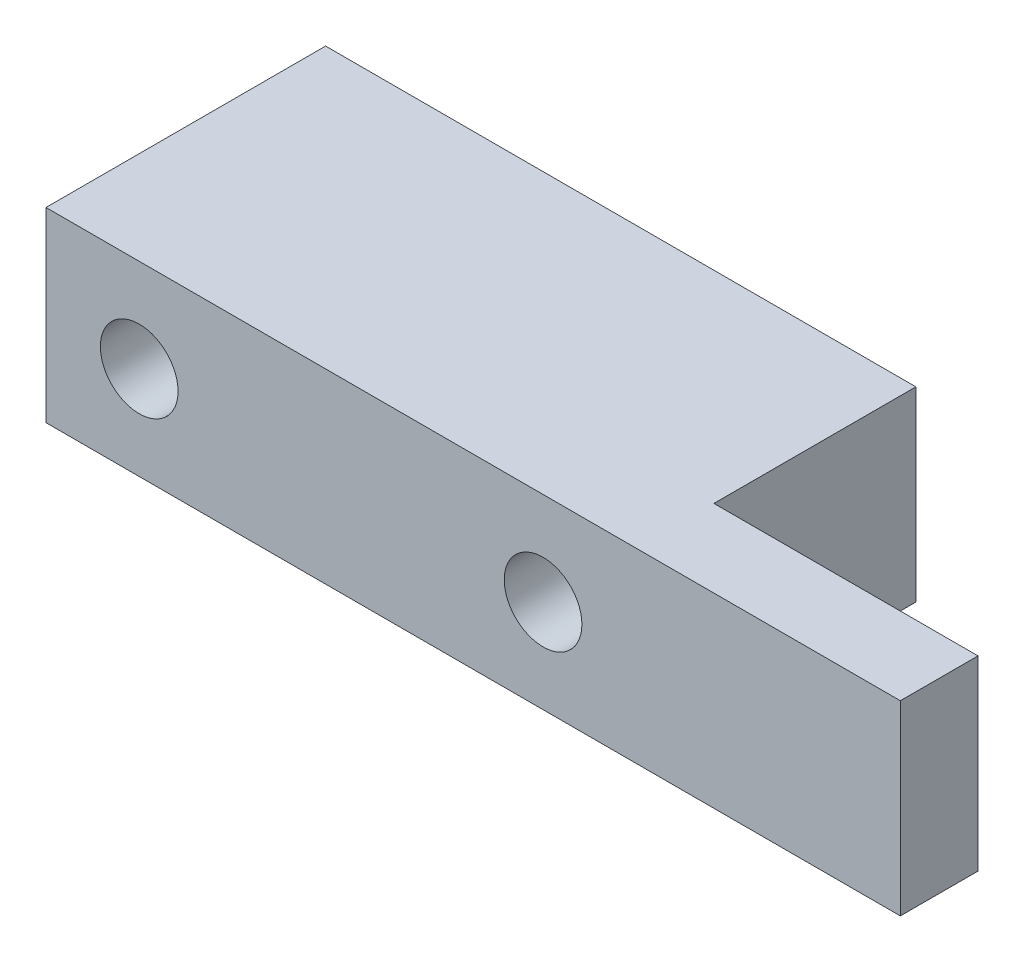
SolidWorks part; units mm, degrees
ref_plane "Front Plane" through (0, 0, 0) normal (1, 0, 0) x (0, 1, 0)
ref_plane "Top Plane" through (0, 0, 0) normal (0, 0, 1) x (0, 1, 0)
ref_plane "Right Plane" through (0, 0, 0) normal (0, 1, 0) x (-1, 0, 0)
sketch "Sketch1" plane through (0, 0, 0) normal (0, 0, 1) x (0, 1, 0)
  line L1 (-3, 9.5) -> (3, 9.5)
  line L2 (-3, 9.5) -> (-3, -9.5)
  line L3 (-3, -9.5) -> (3, -9.5)
  line L4 (3, 9.5) -> (3, -9.5)
  line L5 (-3, 9.5) -> (3, -9.5) construction
  line L6 (-3, -9.5) -> (3, 9.5) construction
  circle A0 centre (0, 6.5) radius 1.25
  circle A1 centre (0, -6.5) radius 1.25
  point P0 (0, 0)
  dimension "D3" = 2.5
  dimension "D4" = 2.5
  dimension "D5" = 3
  dimension "D6" = 3
  dimension "D7" = 3
  dimension "D1" = 19
  dimension "D2" = 6
  dimension "D8" = 3
extrude "Boss-Extrude1" add sketch "Sketch1" along normal blind 9
sketch "Sketch2" plane through (9.5, 0, 0) normal (1, 0, 0) x (0, 1, 0)
  line L0 (3, 9) -> (3, 0) construction
  line L1 (-3, 9) -> (3, 9)
  line L2 (-3, 9) -> (-3, 6.5)
  line L3 (-3, 6.5) -> (3, 6.5)
  line L4 (3, 9) -> (3, 6.5)
  dimension "D1" = 6
  dimension "D2" = 2.5
extrude "Boss-Extrude2" add sketch "Sketch2" along normal blind 8.5
